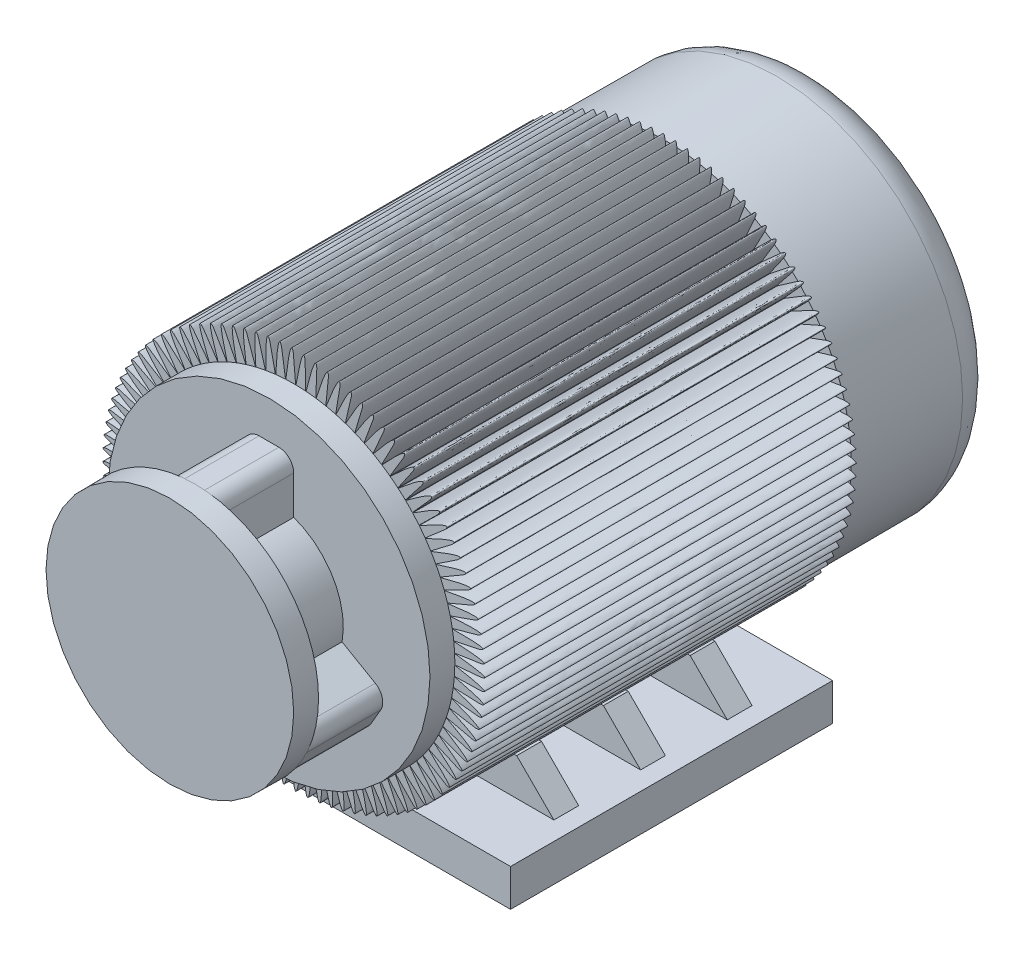
SolidWorks part; units mm, degrees
ref_plane "前视基准面" through (0, 0, 0) normal (0, 0, 1) x (1, 0, 0)
ref_plane "上视基准面" through (0, 0, 0) normal (0, 1, 0) x (1, 0, 0)
ref_plane "右视基准面" through (0, 0, 0) normal (1, 0, 0) x (0, 0, -1)
sketch "草图1" plane through (0, 0, 0) normal (0, 0, 1) x (1, 0, 0)
  circle A0 centre (0, 0) radius 75
  dimension "D1" = 150
extrude "凸台-拉伸1" add sketch "草图1" along normal blind 60
ref_plane "基准面1" through (0, 0, 60) normal (0, 0, 1) x (1, 0, 0)
sketch "草图2" plane through (0, 0, 60) normal (0, 0, 1) x (1, 0, 0)
  arc A0 (4.9696, 64.8097) -> (4.8393, 64.8196) centre (0, 0) ccw
  arc A2 (9.0292, 64.3698) -> (8.8999, 64.3878) centre (0, 0) ccw
  arc A3 (13.0532, 63.6759) -> (12.9252, 63.7019) centre (0, 0) ccw
  arc A4 (17.0257, 62.7306) -> (16.8996, 62.7647) centre (0, 0) ccw
  arc A5 (20.931, 61.5378) -> (20.8073, 61.5797) centre (0, 0) ccw
  arc A6 (24.7536, 60.1021) -> (24.6329, 60.1517) centre (0, 0) ccw
  arc A7 (-60.1021, 24.7536) -> (-60.1517, 24.6329) centre (0, 0) ccw
  arc A8 (-61.5378, 20.931) -> (-61.5797, 20.8073) centre (0, 0) ccw
  arc A9 (-62.7306, 17.0257) -> (-62.7647, 16.8996) centre (0, 0) ccw
  arc A10 (-63.6759, 13.0532) -> (-63.7019, 12.9252) centre (0, 0) ccw
  arc A11 (-64.3698, 9.0292) -> (-64.3878, 8.8999) centre (0, 0) ccw
  arc A12 (-64.9939, 0.8903) -> (-64.9956, 0.7597) centre (0, 0) ccw
  arc A13 (-64.0095, -11.3041) -> (-63.9867, -11.4327) centre (0, 0) ccw
  arc A14 (-63.1734, -15.301) -> (-63.1425, -15.4279) centre (0, 0) ccw
  arc A15 (-62.088, -19.2375) -> (-62.0492, -19.3622) centre (0, 0) ccw
  arc A16 (-60.7575, -23.0981) -> (-60.711, -23.2201) centre (0, 0) ccw
  arc A17 (-59.1873, -26.8675) -> (-59.1332, -26.9863) centre (0, 0) ccw
  arc A18 (-57.3835, -30.5309) -> (-57.3221, -30.6461) centre (0, 0) ccw
  arc A19 (-55.3532, -34.0738) -> (-55.2847, -34.1849) centre (0, 0) ccw
  arc A20 (-53.1045, -37.4822) -> (-53.0291, -37.5888) centre (0, 0) ccw
  arc A21 (-50.6462, -40.7427) -> (-50.5642, -40.8443) centre (0, 0) ccw
  arc A22 (-45.1404, -46.7691) -> (-45.0464, -46.8596) centre (0, 0) ccw
  arc A23 (-32.0912, -56.5257) -> (-31.9776, -56.59) centre (0, 0) ccw
  arc A24 (-28.4786, -58.4292) -> (-28.3612, -58.4863) centre (0, 0) ccw
  arc A25 (-24.7536, -60.1021) -> (-24.6329, -60.1517) centre (0, 0) ccw
  arc A26 (7.2626, -64.593) -> (7.3924, -64.5783) centre (0, 0) ccw
  arc A27 (11.3041, -64.0095) -> (11.4327, -63.9867) centre (0, 0) ccw
  arc A28 (19.2375, -62.088) -> (19.3622, -62.0492) centre (0, 0) ccw
  arc A29 (26.8675, -59.1873) -> (26.9863, -59.1332) centre (0, 0) ccw
  arc A30 (54.3991, -35.5772) -> (54.4705, -35.4678) centre (0, 0) ccw
  arc A31 (-64.9216, -3.1924) -> (-64.915, -3.3229) centre (0, 0) ccw
  arc A32 (-64.593, -7.2626) -> (-64.5783, -7.3924) centre (0, 0) ccw
  arc A33 (-64.8097, 4.9696) -> (-64.8196, 4.8393) centre (0, 0) ccw
  arc A34 (-58.4292, 28.4786) -> (-58.4863, 28.3612) centre (0, 0) ccw
  arc A35 (-56.5257, 32.0912) -> (-56.59, 31.9776) centre (0, 0) ccw
  arc A36 (-54.3991, 35.5772) -> (-54.4705, 35.4678) centre (0, 0) ccw
  arc A37 (-52.0579, 38.9227) -> (-52.1359, 38.8181) centre (0, 0) ccw
  arc A38 (-49.5112, 42.1147) -> (-49.5957, 42.0151) centre (0, 0) ccw
  arc A39 (-46.7691, 45.1404) -> (-46.8596, 45.0464) centre (0, 0) ccw
  arc A40 (-43.8424, 47.988) -> (-43.9387, 47.8998) centre (0, 0) ccw
  arc A41 (-40.7427, 50.6462) -> (-40.8443, 50.5642) centre (0, 0) ccw
  arc A42 (-34.0738, 55.3532) -> (-34.1849, 55.2847) centre (0, 0) ccw
  arc A43 (-30.5309, 57.3835) -> (-30.6461, 57.3221) centre (0, 0) ccw
  arc A44 (-26.8675, 59.1873) -> (-26.9863, 59.1332) centre (0, 0) ccw
  arc A45 (-37.4822, 53.1045) -> (-37.5888, 53.0291) centre (0, 0) ccw
  arc A46 (-23.0981, 60.7575) -> (-23.2201, 60.711) centre (0, 0) ccw
  arc A47 (-19.2375, 62.088) -> (-19.3622, 62.0492) centre (0, 0) ccw
  arc A48 (-15.301, 63.1734) -> (-15.4279, 63.1425) centre (0, 0) ccw
  arc A49 (-11.3041, 64.0095) -> (-11.4327, 63.9867) centre (0, 0) ccw
  arc A50 (-7.2626, 64.593) -> (-7.3924, 64.5783) centre (0, 0) ccw
  arc A51 (-3.1924, 64.9216) -> (-3.3229, 64.915) centre (0, 0) ccw
  arc A52 (0.8903, 64.9939) -> (0.7597, 64.9956) centre (0, 0) ccw
  arc A53 (45.1404, 46.7691) -> (45.0464, 46.8596) centre (0, 0) ccw
  arc A54 (42.1147, 49.5112) -> (42.0151, 49.5957) centre (0, 0) ccw
  arc A55 (32.0912, 56.5257) -> (31.9776, 56.59) centre (0, 0) ccw
  arc A56 (28.4786, 58.4292) -> (28.3612, 58.4863) centre (0, 0) ccw
  arc A57 (35.5772, 54.3991) -> (35.4678, 54.4705) centre (0, 0) ccw
  arc A58 (38.9227, 52.0579) -> (38.8181, 52.1359) centre (0, 0) ccw
  arc A59 (47.988, 43.8424) -> (47.8998, 43.9387) centre (0, 0) ccw
  arc A60 (60.7575, 23.0981) -> (60.711, 23.2201) centre (0, 0) ccw
  arc A61 (62.088, 19.2375) -> (62.0492, 19.3622) centre (0, 0) ccw
  arc A62 (63.1734, 15.301) -> (63.1425, 15.4279) centre (0, 0) ccw
  arc A63 (64.0095, 11.3041) -> (63.9867, 11.4327) centre (0, 0) ccw
  arc A64 (64.593, 7.2626) -> (64.5783, 7.3924) centre (0, 0) ccw
  arc A65 (59.1873, 26.8675) -> (59.1332, 26.9863) centre (0, 0) ccw
  arc A66 (57.3835, 30.5309) -> (57.3221, 30.6461) centre (0, 0) ccw
  arc A67 (55.3532, 34.0738) -> (55.2847, 34.1849) centre (0, 0) ccw
  arc A68 (53.1045, 37.4822) -> (53.0291, 37.5888) centre (0, 0) ccw
  arc A69 (50.6462, 40.7427) -> (50.5642, 40.8443) centre (0, 0) ccw
  arc A70 (64.9216, 3.1924) -> (64.915, 3.3229) centre (0, 0) ccw
  arc A71 (64.9939, -0.8903) -> (64.9956, -0.7597) centre (0, 0) ccw
  arc A72 (64.8097, -4.9696) -> (64.8196, -4.8393) centre (0, 0) ccw
  arc A73 (64.3698, -9.0292) -> (64.3878, -8.8999) centre (0, 0) ccw
  arc A74 (63.6759, -13.0532) -> (63.7019, -12.9252) centre (0, 0) ccw
  arc A75 (62.7306, -17.0257) -> (62.7647, -16.8996) centre (0, 0) ccw
  arc A76 (52.0579, -38.9227) -> (52.1359, -38.8181) centre (0, 0) ccw
  arc A77 (49.5112, -42.1147) -> (49.5957, -42.0151) centre (0, 0) ccw
  arc A78 (46.7691, -45.1404) -> (46.8596, -45.0464) centre (0, 0) ccw
  arc A79 (43.8424, -47.988) -> (43.9387, -47.8998) centre (0, 0) ccw
  arc A80 (40.7427, -50.6462) -> (40.8443, -50.5642) centre (0, 0) ccw
  arc A81 (37.4822, -53.1045) -> (37.5888, -53.0291) centre (0, 0) ccw
  arc A82 (34.0738, -55.3532) -> (34.1849, -55.2847) centre (0, 0) ccw
  arc A83 (30.5309, -57.3835) -> (30.6461, -57.3221) centre (0, 0) ccw
  arc A84 (23.0981, -60.7575) -> (23.2201, -60.711) centre (0, 0) ccw
  arc A85 (15.301, -63.1734) -> (15.4279, -63.1425) centre (0, 0) ccw
  arc A86 (3.1924, -64.9216) -> (3.3229, -64.915) centre (0, 0) ccw
  arc A87 (-0.8903, -64.9939) -> (-0.7597, -64.9956) centre (0, 0) ccw
  arc A88 (-4.9696, -64.8097) -> (-4.8393, -64.8196) centre (0, 0) ccw
  arc A89 (56.5257, -32.0912) -> (56.59, -31.9776) centre (0, 0) ccw
  arc A90 (61.5378, -20.931) -> (61.5797, -20.8073) centre (0, 0) ccw
  arc A91 (60.1021, -24.7536) -> (60.1517, -24.6329) centre (0, 0) ccw
  arc A92 (58.4292, -28.4786) -> (58.4863, -28.3612) centre (0, 0) ccw
  arc A93 (-20.931, -61.5378) -> (-20.8073, -61.5797) centre (0, 0) ccw
  arc A94 (-17.0257, -62.7306) -> (-16.8996, -62.7647) centre (0, 0) ccw
  arc A95 (-13.0532, -63.6759) -> (-12.9252, -63.7019) centre (0, 0) ccw
  arc A96 (-9.0292, -64.3698) -> (-8.8999, -64.3878) centre (0, 0) ccw
  arc A97 (-35.5772, -54.3991) -> (-35.4678, -54.4705) centre (0, 0) ccw
  arc A98 (-38.9227, -52.0579) -> (-38.8181, -52.1359) centre (0, 0) ccw
  arc A99 (-42.1147, -49.5112) -> (-42.0151, -49.5957) centre (0, 0) ccw
  arc A100 (-47.988, -43.8424) -> (-47.8998, -43.9387) centre (0, 0) ccw
  circle A101 centre (0, 0) radius 65 construction
  spline S0 degree 2 poles (-3.1924, 64.9216) (-0.3704, 89.2037) (0.7597, 64.9956) knots 0 0 0 1 1 1
  spline S1 degree 2 poles (0.8903, 64.9939) (5.2315, 89.051) (4.8393, 64.8196) knots 0 0 0 1 1 1
  spline S2 degree 2 poles (4.9696, 64.8097) (10.8128, 88.5468) (8.8999, 64.3878) knots 0 0 0 1 1 1
  spline S3 degree 2 poles (9.0292, 64.3698) (16.3513, 87.6931) (12.9252, 63.7019) knots 0 0 0 1 1 1
  spline S4 degree 2 poles (13.0532, 63.6759) (21.8254, 86.4933) (16.8996, 62.7647) knots 0 0 0 1 1 1
  spline S5 degree 2 poles (17.0257, 62.7306) (27.2132, 84.9522) (20.8073, 61.5797) knots 0 0 0 1 1 1
  spline S6 degree 2 poles (20.931, 61.5378) (32.4937, 83.0759) (24.6329, 60.1517) knots 0 0 0 1 1 1
  spline S7 degree 2 poles (24.7536, 60.1021) (37.646, 80.8716) (28.3612, 58.4863) knots 0 0 0 1 1 1
  spline S8 degree 2 poles (28.4786, 58.4292) (42.6497, 78.3483) (31.9776, 56.59) knots 0 0 0 1 1 1
  spline S9 degree 2 poles (32.0912, 56.5257) (47.4851, 75.5157) (35.4678, 54.4705) knots 0 0 0 1 1 1
  spline S10 degree 2 poles (35.5772, 54.3991) (52.133, 72.385) (38.8181, 52.1359) knots 0 0 0 1 1 1
  spline S11 degree 2 poles (38.9227, 52.0579) (56.5752, 68.9687) (42.0151, 49.5957) knots 0 0 0 1 1 1
  spline S12 degree 2 poles (42.1147, 49.5112) (60.7942, 65.2803) (45.0464, 46.8596) knots 0 0 0 1 1 1
  spline S13 degree 2 poles (45.1404, 46.7691) (64.7732, 61.3341) (47.8998, 43.9387) knots 0 0 0 1 1 1
  spline S14 degree 2 poles (47.988, 43.8424) (68.4966, 57.146) (50.5642, 40.8443) knots 0 0 0 1 1 1
  spline S15 degree 2 poles (50.6462, 40.7427) (71.9497, 52.7323) (53.0291, 37.5888) knots 0 0 0 1 1 1
  spline S16 degree 2 poles (53.1045, 37.4822) (75.1188, 48.1105) (55.2847, 34.1849) knots 0 0 0 1 1 1
  spline S17 degree 2 poles (55.3532, 34.0738) (77.9914, 43.2988) (57.3221, 30.6461) knots 0 0 0 1 1 1
  spline S18 degree 2 poles (57.3835, 30.5309) (80.5563, 38.3162) (59.1332, 26.9863) knots 0 0 0 1 1 1
  spline S19 degree 2 poles (59.1873, 26.8675) (82.8032, 33.1824) (60.711, 23.2201) knots 0 0 0 1 1 1
  spline S20 degree 2 poles (60.7575, 23.0981) (84.7234, 27.9177) (62.0492, 19.3622) knots 0 0 0 1 1 1
  spline S21 degree 2 poles (62.088, 19.2375) (86.3091, 22.5428) (63.1425, 15.4279) knots 0 0 0 1 1 1
  spline S22 degree 2 poles (63.1734, 15.301) (87.5543, 17.0789) (63.9867, 11.4327) knots 0 0 0 1 1 1
  spline S23 degree 2 poles (64.0095, 11.3041) (88.4539, 11.5476) (64.5783, 7.3924) knots 0 0 0 1 1 1
  spline S24 degree 2 poles (64.593, 7.2626) (89.0045, 5.9708) (64.915, 3.3229) knots 0 0 0 1 1 1
  spline S25 degree 2 poles (64.9216, 3.1924) (89.2037, 0.3704) (64.9956, -0.7597) knots 0 0 0 1 1 1
  spline S26 degree 2 poles (64.9939, -0.8903) (89.051, -5.2315) (64.8196, -4.8393) knots 0 0 0 1 1 1
  spline S27 degree 2 poles (64.8097, -4.9696) (88.5468, -10.8128) (64.3878, -8.8999) knots 0 0 0 1 1 1
  spline S28 degree 2 poles (64.3698, -9.0292) (87.6931, -16.3513) (63.7019, -12.9252) knots 0 0 0 1 1 1
  spline S29 degree 2 poles (63.6759, -13.0532) (86.4933, -21.8254) (62.7647, -16.8996) knots 0 0 0 1 1 1
  spline S30 degree 2 poles (62.7306, -17.0257) (84.9522, -27.2132) (61.5797, -20.8073) knots 0 0 0 1 1 1
  spline S31 degree 2 poles (61.5378, -20.931) (83.0759, -32.4937) (60.1517, -24.6329) knots 0 0 0 1 1 1
  spline S32 degree 2 poles (60.1021, -24.7536) (80.8716, -37.646) (58.4863, -28.3612) knots 0 0 0 1 1 1
  spline S33 degree 2 poles (58.4292, -28.4786) (78.3483, -42.6497) (56.59, -31.9776) knots 0 0 0 1 1 1
  spline S34 degree 2 poles (56.5257, -32.0912) (75.5157, -47.4851) (54.4705, -35.4678) knots 0 0 0 1 1 1
  spline S35 degree 2 poles (54.3991, -35.5772) (72.385, -52.133) (52.1359, -38.8181) knots 0 0 0 1 1 1
  spline S36 degree 2 poles (52.0579, -38.9227) (68.9687, -56.5752) (49.5957, -42.0151) knots 0 0 0 1 1 1
  spline S37 degree 2 poles (49.5112, -42.1147) (65.2803, -60.7942) (46.8596, -45.0464) knots 0 0 0 1 1 1
  spline S38 degree 2 poles (46.7691, -45.1404) (61.3341, -64.7732) (43.9387, -47.8998) knots 0 0 0 1 1 1
  spline S39 degree 2 poles (43.8424, -47.988) (57.146, -68.4966) (40.8443, -50.5642) knots 0 0 0 1 1 1
  spline S40 degree 2 poles (40.7427, -50.6462) (52.7323, -71.9497) (37.5888, -53.0291) knots 0 0 0 1 1 1
  spline S41 degree 2 poles (37.4822, -53.1045) (48.1105, -75.1188) (34.1849, -55.2847) knots 0 0 0 1 1 1
  spline S42 degree 2 poles (34.0738, -55.3532) (43.2988, -77.9914) (30.6461, -57.3221) knots 0 0 0 1 1 1
  spline S43 degree 2 poles (30.5309, -57.3835) (38.3162, -80.5563) (26.9863, -59.1332) knots 0 0 0 1 1 1
  spline S44 degree 2 poles (26.8675, -59.1873) (33.1824, -82.8032) (23.2201, -60.711) knots 0 0 0 1 1 1
  spline S45 degree 2 poles (23.0981, -60.7575) (27.9177, -84.7234) (19.3622, -62.0492) knots 0 0 0 1 1 1
  spline S46 degree 2 poles (19.2375, -62.088) (22.5428, -86.3091) (15.4279, -63.1425) knots 0 0 0 1 1 1
  spline S47 degree 2 poles (15.301, -63.1734) (17.0789, -87.5543) (11.4327, -63.9867) knots 0 0 0 1 1 1
  spline S48 degree 2 poles (11.3041, -64.0095) (11.5476, -88.4539) (7.3924, -64.5783) knots 0 0 0 1 1 1
  spline S49 degree 2 poles (7.2626, -64.593) (5.9708, -89.0045) (3.3229, -64.915) knots 0 0 0 1 1 1
  spline S50 degree 2 poles (3.1924, -64.9216) (0.3704, -89.2037) (-0.7597, -64.9956) knots 0 0 0 1 1 1
  spline S51 degree 2 poles (-0.8903, -64.9939) (-5.2315, -89.051) (-4.8393, -64.8196) knots 0 0 0 1 1 1
  spline S52 degree 2 poles (-4.9696, -64.8097) (-10.8128, -88.5468) (-8.8999, -64.3878) knots 0 0 0 1 1 1
  spline S53 degree 2 poles (-9.0292, -64.3698) (-16.3513, -87.6931) (-12.9252, -63.7019) knots 0 0 0 1 1 1
  spline S54 degree 2 poles (-13.0532, -63.6759) (-21.8254, -86.4933) (-16.8996, -62.7647) knots 0 0 0 1 1 1
  spline S55 degree 2 poles (-17.0257, -62.7306) (-27.2132, -84.9522) (-20.8073, -61.5797) knots 0 0 0 1 1 1
  spline S56 degree 2 poles (-20.931, -61.5378) (-32.4937, -83.0759) (-24.6329, -60.1517) knots 0 0 0 1 1 1
  spline S57 degree 2 poles (-24.7536, -60.1021) (-37.646, -80.8716) (-28.3612, -58.4863) knots 0 0 0 1 1 1
  spline S58 degree 2 poles (-28.4786, -58.4292) (-42.6497, -78.3483) (-31.9776, -56.59) knots 0 0 0 1 1 1
  spline S59 degree 2 poles (-32.0912, -56.5257) (-47.4851, -75.5157) (-35.4678, -54.4705) knots 0 0 0 1 1 1
  spline S60 degree 2 poles (-35.5772, -54.3991) (-52.133, -72.385) (-38.8181, -52.1359) knots 0 0 0 1 1 1
  spline S61 degree 2 poles (-38.9227, -52.0579) (-56.5752, -68.9687) (-42.0151, -49.5957) knots 0 0 0 1 1 1
  spline S62 degree 2 poles (-42.1147, -49.5112) (-60.7942, -65.2803) (-45.0464, -46.8596) knots 0 0 0 1 1 1
  spline S63 degree 2 poles (-45.1404, -46.7691) (-64.7732, -61.3341) (-47.8998, -43.9387) knots 0 0 0 1 1 1
  spline S64 degree 2 poles (-47.988, -43.8424) (-68.4966, -57.146) (-50.5642, -40.8443) knots 0 0 0 1 1 1
  spline S65 degree 2 poles (-50.6462, -40.7427) (-71.9497, -52.7323) (-53.0291, -37.5888) knots 0 0 0 1 1 1
  spline S66 degree 2 poles (-53.1045, -37.4822) (-75.1188, -48.1105) (-55.2847, -34.1849) knots 0 0 0 1 1 1
  spline S67 degree 2 poles (-55.3532, -34.0738) (-77.9914, -43.2988) (-57.3221, -30.6461) knots 0 0 0 1 1 1
  spline S68 degree 2 poles (-57.3835, -30.5309) (-80.5563, -38.3162) (-59.1332, -26.9863) knots 0 0 0 1 1 1
  spline S69 degree 2 poles (-59.1873, -26.8675) (-82.8032, -33.1824) (-60.711, -23.2201) knots 0 0 0 1 1 1
  spline S70 degree 2 poles (-60.7575, -23.0981) (-84.7234, -27.9177) (-62.0492, -19.3622) knots 0 0 0 1 1 1
  spline S71 degree 2 poles (-62.088, -19.2375) (-86.3091, -22.5428) (-63.1425, -15.4279) knots 0 0 0 1 1 1
  spline S72 degree 2 poles (-63.1734, -15.301) (-87.5543, -17.0789) (-63.9867, -11.4327) knots 0 0 0 1 1 1
  spline S73 degree 2 poles (-64.0095, -11.3041) (-88.4539, -11.5476) (-64.5783, -7.3924) knots 0 0 0 1 1 1
  spline S74 degree 2 poles (-64.593, -7.2626) (-89.0045, -5.9708) (-64.915, -3.3229) knots 0 0 0 1 1 1
  spline S75 degree 2 poles (-64.9216, -3.1924) (-89.2037, -0.3704) (-64.9956, 0.7597) knots 0 0 0 1 1 1
  spline S76 degree 2 poles (-64.9939, 0.8903) (-89.051, 5.2315) (-64.8196, 4.8393) knots 0 0 0 1 1 1
  spline S77 degree 2 poles (-64.8097, 4.9696) (-88.5468, 10.8128) (-64.3878, 8.8999) knots 0 0 0 1 1 1
  spline S78 degree 2 poles (-64.3698, 9.0292) (-87.6931, 16.3513) (-63.7019, 12.9252) knots 0 0 0 1 1 1
  spline S79 degree 2 poles (-63.6759, 13.0532) (-86.4933, 21.8254) (-62.7647, 16.8996) knots 0 0 0 1 1 1
  spline S80 degree 2 poles (-62.7306, 17.0257) (-84.9522, 27.2132) (-61.5797, 20.8073) knots 0 0 0 1 1 1
  spline S81 degree 2 poles (-61.5378, 20.931) (-83.0759, 32.4937) (-60.1517, 24.6329) knots 0 0 0 1 1 1
  spline S82 degree 2 poles (-60.1021, 24.7536) (-80.8716, 37.646) (-58.4863, 28.3612) knots 0 0 0 1 1 1
  spline S83 degree 2 poles (-58.4292, 28.4786) (-78.3483, 42.6497) (-56.59, 31.9776) knots 0 0 0 1 1 1
  spline S84 degree 2 poles (-56.5257, 32.0912) (-75.5157, 47.4851) (-54.4705, 35.4678) knots 0 0 0 1 1 1
  spline S85 degree 2 poles (-54.3991, 35.5772) (-72.385, 52.133) (-52.1359, 38.8181) knots 0 0 0 1 1 1
  spline S86 degree 2 poles (-52.0579, 38.9227) (-68.9687, 56.5752) (-49.5957, 42.0151) knots 0 0 0 1 1 1
  spline S87 degree 2 poles (-49.5112, 42.1147) (-65.2803, 60.7942) (-46.8596, 45.0464) knots 0 0 0 1 1 1
  spline S88 degree 2 poles (-46.7691, 45.1404) (-61.3341, 64.7732) (-43.9387, 47.8998) knots 0 0 0 1 1 1
  spline S89 degree 2 poles (-43.8424, 47.988) (-57.146, 68.4966) (-40.8443, 50.5642) knots 0 0 0 1 1 1
  spline S90 degree 2 poles (-40.7427, 50.6462) (-52.7323, 71.9497) (-37.5888, 53.0291) knots 0 0 0 1 1 1
  spline S91 degree 2 poles (-37.4822, 53.1045) (-48.1105, 75.1188) (-34.1849, 55.2847) knots 0 0 0 1 1 1
  spline S92 degree 2 poles (-34.0738, 55.3532) (-43.2988, 77.9914) (-30.6461, 57.3221) knots 0 0 0 1 1 1
  spline S93 degree 2 poles (-30.5309, 57.3835) (-38.3162, 80.5563) (-26.9863, 59.1332) knots 0 0 0 1 1 1
  spline S94 degree 2 poles (-26.8675, 59.1873) (-33.1824, 82.8032) (-23.2201, 60.711) knots 0 0 0 1 1 1
  spline S95 degree 2 poles (-23.0981, 60.7575) (-27.9177, 84.7234) (-19.3622, 62.0492) knots 0 0 0 1 1 1
  spline S96 degree 2 poles (-19.2375, 62.088) (-22.5428, 86.3091) (-15.4279, 63.1425) knots 0 0 0 1 1 1
  spline S97 degree 2 poles (-15.301, 63.1734) (-17.0789, 87.5543) (-11.4327, 63.9867) knots 0 0 0 1 1 1
  spline S98 degree 2 poles (-11.3041, 64.0095) (-11.5476, 88.4539) (-7.3924, 64.5783) knots 0 0 0 1 1 1
  spline S99 degree 2 poles (-7.2626, 64.593) (-5.9708, 89.0045) (-3.3229, 64.915) knots 0 0 0 1 1 1
  point P306 (0, 0)
extrude "凸台-拉伸3" add sketch "草图2" along normal blind 150
fillet "圆角2" radius 15 1 edges at (75, 0, 0)
ref_plane "基准面2" through (0, 0, 210) normal (0, 0, 1) x (1, 0, 0)
sketch "草图3" plane through (0, 0, 210) normal (0, 0, 1) x (1, 0, 0)
  circle A0 centre (0, 0) radius 65
  dimension "D1" = 130
extrude "凸台-拉伸4" add sketch "草图3" along normal blind 10
ref_plane "基准面3" through (0, 0, 220) normal (0, 0, 1) x (1, 0, 0)
sketch "草图4" plane through (0, 0, 220) normal (0, 0, 1) x (1, 0, 0)
  line L0 (-10, 28.2843) -> (-10, 43.7909)
  line L1 (-4, 49.7909) -> (4, 49.7909)
  line L2 (10, 43.7909) -> (10, 28.2843)
  line L3 (0, 0) -> (0, 61.3702) construction
  line L4 (29.4949, -5.4819) -> (42.924, -13.2352)
  line L5 (45.1202, -21.4314) -> (41.1202, -28.3596)
  line L6 (32.924, -30.5557) -> (19.4949, -22.8024)
  line L7 (-19.4949, -22.8024) -> (-32.924, -30.5557)
  line L8 (-41.1202, -28.3596) -> (-45.1202, -21.4314)
  line L9 (-42.924, -13.2352) -> (-29.4949, -5.4819)
  arc A0 (-10, 28.2843) -> (-29.4949, -5.4819) centre (0, 0) ccw
  arc A1 (-4, 49.7909) -> (-10, 43.7909) centre (-4, 43.7909) ccw
  arc A2 (10, 43.7909) -> (4, 49.7909) centre (4, 43.7909) ccw
  arc A3 (45.1202, -21.4314) -> (42.924, -13.2352) centre (39.924, -18.4314) ccw
  arc A4 (32.924, -30.5557) -> (41.1202, -28.3596) centre (35.924, -25.3596) ccw
  arc A5 (-41.1202, -28.3596) -> (-32.924, -30.5557) centre (-35.924, -25.3596) ccw
  arc A6 (-42.924, -13.2352) -> (-45.1202, -21.4314) centre (-39.924, -18.4314) ccw
  arc A7 (-19.4949, -22.8024) -> (19.4949, -22.8024) centre (0, 0) ccw
  arc A8 (29.4949, -5.4819) -> (10, 28.2843) centre (0, 0) ccw
  point P11 (-10, 49.7909)
  point P14 (10, 49.7909)
  point P34 (0, 0)
  dimension "D1" = 60
  dimension "D4" = 6
  dimension "D5" = 6
  dimension "D2" = 20
  dimension "D3" = 10
  dimension "D6" = 3
extrude "凸台-拉伸5" add sketch "草图4" along normal blind 30
ref_plane "基准面4" through (0, 0, 250) normal (0, 0, 1) x (1, 0, 0)
sketch "草图5" plane through (0, 0, 250) normal (0, 0, 1) x (1, 0, 0)
  circle A0 centre (0, 0) radius 50
  dimension "D1" = 100
extrude "凸台-拉伸6" add sketch "草图5" along normal blind 10
ref_plane "基准面5" through (0, -85, 0) normal (0, 1, 0) x (1, 0, 0)
sketch "草图6" plane through (0, -85, 0) normal (0, 1, 0) x (1, 0, 0)
  line L0 (0, 269.5978) -> (0, -269.5978) construction
  line L1 (-77.5, -200) -> (77.5, -200)
  line L2 (-77.5, -200) -> (-77.5, -70)
  line L3 (-77.5, -70) -> (77.5, -70)
  line L4 (77.5, -200) -> (77.5, -70)
  line L5 (-2.2798, -210) -> (2.2798, -210) construction
  point P5 (0, 0)
  dimension "D1" = 155
  dimension "D2" = 130
  dimension "D3" = 77.5
  dimension "D4" = 10
extrude "凸台-拉伸7" add sketch "草图6" along normal blind 15
sketch "草图7" plane through (0, 0, 0) normal (1, 0, 0) x (0, 0, -1)
  line L0 (-200, -70) -> (-70, -70) construction
  line L1 (-70, -70) -> (-200, -70) construction
  line L2 (-175, -55) -> (-165, -55)
  line L3 (-175, -55) -> (-175, -70)
  line L4 (-175, -70) -> (-165, -70)
  line L5 (-140, -55) -> (-130, -55)
  line L6 (-165, -55) -> (-165, -70)
  line L7 (-140, -55) -> (-140, -70)
  line L8 (-140, -70) -> (-130, -70)
  line L9 (-130, -55) -> (-130, -70)
  line L10 (-105, -55) -> (-95, -55)
  line L11 (-105, -55) -> (-105, -70)
  line L12 (-105, -70) -> (-95, -70)
  line L13 (-95, -55) -> (-95, -70)
  dimension "D1" = 15
  dimension "D2" = 25
  dimension "D3" = 10
  dimension "D4" = 15
  dimension "D5" = 15
  dimension "D6" = 25
  dimension "D7" = 25
  dimension "D8" = 10
  dimension "D9" = 10
extrude "凸台-拉伸8" add sketch "草图7" along normal blind 70
ref_plane "基准面6" through (0, 0, 175) normal (0, 0, 1) x (1, 0, 0)
sketch "草图8" plane through (0, 0, 175) normal (0, 0, 1) x (1, 0, 0)
  line L0 (70, -55) -> (55, -55)
  line L1 (70, -55) -> (53.3054, -55) construction
  line L2 (55, -55) -> (70, -70)
  line L3 (70, -55) -> (70, -70) construction
  line L4 (70, -70) -> (70, -55)
  dimension "D1" = 15
  dimension "D2" = 15
extrude "切除-拉伸1" cut sketch "草图8" against normal blind 85
mirror "镜向1" about plane through (0, 0, 0) normal (1, 0, 0) of "凸台-拉伸8", "切除-拉伸1"
